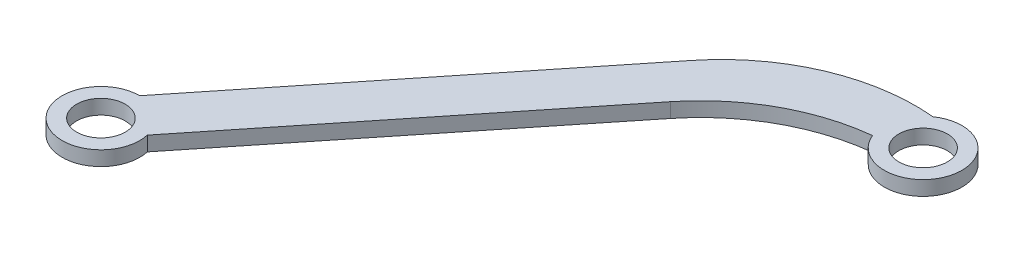
SolidWorks part; units mm, degrees
ref_plane "前视基准面" through (0, 0, 0) normal (0, 0, 1) x (1, 0, 0)
ref_plane "上视基准面" through (0, 0, 0) normal (0, 1, 0) x (1, 0, 0)
ref_plane "右视基准面" through (0, 0, 0) normal (1, 0, 0) x (0, 0, -1)
other "Configuration Table"
sketch "草图1" plane through (0, 0, 0) normal (0, 1, 0) x (1, 0, 0)
  line L0 (-23.1364, 12.1401) -> (-4.55, 6.5801)
  line L1 (-23.1364, 12.1401) -> (-90, -71.3725)
  line L2 (-82.1938, -77.6225) -> (-19.5436, 0.6275)
  line L3 (-19.5436, 0.6275) -> (-7.416, -3.0005)
  arc A0 (-7.416, -3.0005) -> (-4.55, 6.5801) centre (0, 0) ccw
  arc A1 (-90, -71.3725) -> (-82.1938, -77.6225) centre (-90, -79.3725) ccw
  dimension "D1" = 16
  dimension "D2" = 16
  dimension "D3" = 120
  dimension "D9" = 90
  dimension "D4" = 10
  dimension "D5" = 10
  dimension "D6" = 5
  dimension "D7" = 5
  dimension "D8" = 80
extrude "凸台-拉伸1" add sketch "草图1" along normal blind 3
fillet "圆角1" radius 40 2 edges at (-23.1364, 1.5, -12.1401) (-19.5436, 1.5, -0.6275)
sketch "草图2" plane through (0, 3, 0) normal (0, 1, 0) x (1, 0, 0)
  circle A0 centre (-90, -79.3725) radius 5
  dimension "D1" = 10
extrude "切除-拉伸1" cut sketch "草图2" against normal blind 5
sketch "草图3" plane through (0, 3, 0) normal (0, 1, 0) x (1, 0, 0)
  circle A0 centre (0, 0) radius 5
  dimension "D1" = 10
extrude "切除-拉伸2" cut sketch "草图3" against normal blind 5
